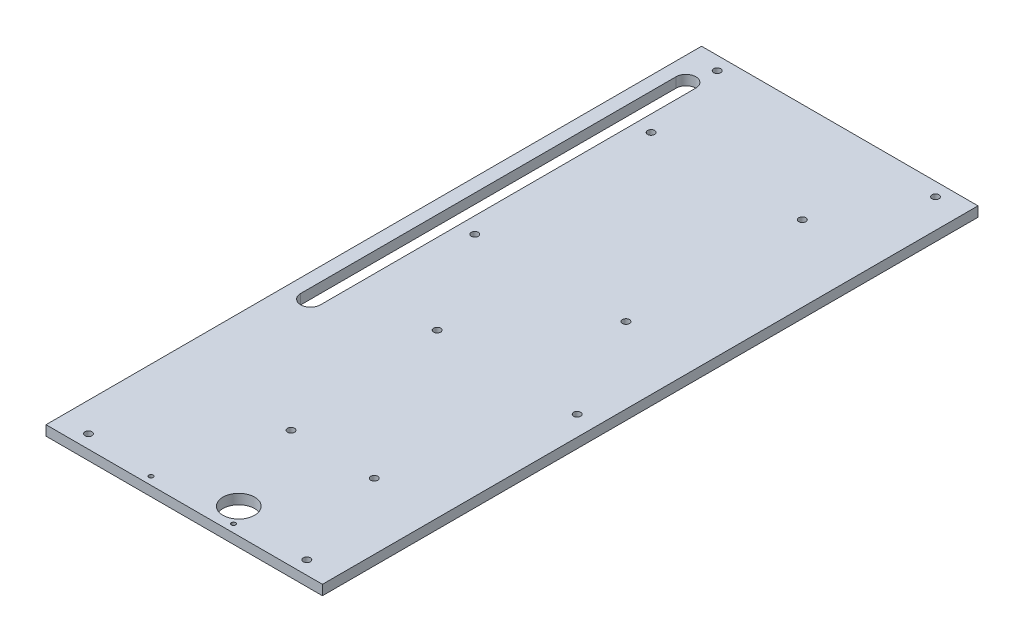
SolidWorks part; units mm, degrees
ref_plane "Front Plane" through (0, 0, 0) normal (0, 0, 1) x (1, 0, 0)
ref_plane "Top Plane" through (0, 0, 0) normal (0, 1, 0) x (1, 0, 0)
ref_plane "Right Plane" through (0, 0, 0) normal (1, 0, 0) x (0, 0, -1)
sketch "Sketch2" plane through (0, 0, 0) normal (0, 0, 1) x (1, 0, 0)
  line L0 (42.8242, -21.393) -> (42.8242, -24.5934)
  line L1 (0, -21.393) -> (0, -24.5934) construction
  line L2 (-46.0758, -24.5934) -> (42.8242, -24.5934)
  line L3 (-46.0758, -21.393) -> (-46.0758, -24.5934)
  line L4 (-46.0758, -21.393) -> (42.8242, -21.393)
  dimension "D1" = 88.9
  dimension "D2" = 3.2004
extrude "Boss-Extrude1" add sketch "Sketch2" along normal blind 210.82 contours L2 L0 L4 L3
sketch "Sketch3" plane through (0, -21.393, 0) normal (0, 1, 0) x (-1, 0, 0)
  line L0 (-42.8242, 208.28) -> (46.0758, 208.28) construction
  line L1 (38.5043, 9.421) -> (38.5043, 0) construction
  line L2 (46.0758, 0) -> (-42.8242, 0) construction
  line L3 (46.0758, 210.82) -> (-42.8242, 210.82) construction
  line L4 (36.73, 206.502) -> (46.0758, 206.502) construction
  line L5 (46.0758, 72.9493) -> (41.6793, 72.9493) construction
  line L6 (35.3293, 12.596) -> (41.6793, 12.596) construction
  line L7 (35.3293, 12.596) -> (35.3293, 133.3026)
  line L8 (35.3293, 133.3026) -> (41.6793, 133.3026) construction
  line L9 (41.6793, 12.596) -> (41.6793, 133.3026)
  line L10 (46.0758, 210.82) -> (-42.8242, 210.82) construction
  line L11 (-11.6838, 208.28) -> (-11.6838, 210.82) construction
  line L12 (-11.6838, 202.5188) -> (-11.6838, 208.28) construction
  line L13 (-7.6198, 202.5188) -> (-11.6838, 202.5188) construction
  line L14 (-42.8242, 210.82) -> (-42.8242, 0) construction
  line L15 (46.0758, 210.82) -> (46.0758, 0) construction
  line L16 (-33.4785, 206.502) -> (-33.4785, 210.82) construction
  line L17 (-33.4785, 206.502) -> (-42.8242, 206.502) construction
  line L18 (36.73, 206.502) -> (36.73, 210.82) construction
  line L19 (-33.4785, 4.318) -> (-42.8242, 4.318) construction
  line L20 (-33.4785, 4.318) -> (-33.4785, 0) construction
  line L21 (46.0758, 0) -> (-42.8242, 0) construction
  line L22 (36.73, 4.318) -> (36.73, 0) construction
  line L23 (36.73, 4.318) -> (46.0758, 4.318) construction
  line L24 (-18.451, 32.1211) -> (-18.451, 0) construction
  line L25 (-42.8242, 32.1211) -> (-18.451, 32.1211) construction
  line L26 (-18.451, 32.1211) -> (30.1646, 32.1211) construction
  line L27 (-18.451, 32.1211) -> (-18.451, 88.8393) construction
  line L28 (30.1646, 32.1211) -> (30.1646, 88.8393) construction
  line L29 (-18.451, 88.8393) -> (30.1646, 88.8393) construction
  line L30 (-42.8242, 122.5046) -> (-36.4214, 122.5046) construction
  line L31 (-36.4214, 122.5046) -> (-36.4214, 0) construction
  line L32 (5.127, 172.9556) -> (9.5159, 121.5883) construction
  line L33 (-21.6121, 172.9556) -> (5.127, 172.9556) construction
  line L34 (60.367, -163.7177) -> (66.7698, -163.7177) construction
  line L35 (66.7698, -163.7177) -> (96.7645, -163.7177) construction
  line L36 (-21.6121, 172.9556) -> (-36.4214, 122.5046) construction
  line L37 (81.5791, -113.2668) -> (108.3182, -113.2668) construction
  line L38 (81.5791, -113.2668) -> (66.7698, -163.7177) construction
  line L39 (76.3923, -158.9273) -> (82.7952, -158.9273) construction
  line L40 (82.7952, -158.9273) -> (112.7898, -158.9273) construction
  line L41 (97.6044, -108.4763) -> (124.3436, -108.4763) construction
  line L42 (97.6044, -108.4763) -> (82.7952, -158.9273) construction
  circle A0 centre (14.8338, 208.28) radius 0.6731
  arc A1 (35.3293, 133.3026) -> (41.6793, 133.3026) centre (38.5043, 133.3026) cw
  arc A2 (41.6793, 12.596) -> (35.3293, 12.596) centre (38.5043, 12.596) cw
  circle A3 centre (-11.6838, 208.28) radius 0.6731
  circle A4 centre (-7.6198, 202.5188) radius 5.08
  circle A5 centre (-33.4785, 206.502) radius 1.1303
  circle A6 centre (36.73, 206.502) radius 1.1303
  circle A7 centre (-33.4785, 4.318) radius 1.1303
  circle A8 centre (36.73, 4.318) radius 1.1303
  circle A9 centre (-18.451, 32.1211) radius 1.1303
  circle A10 centre (-18.451, 88.8393) radius 1.1303
  circle A11 centre (30.1646, 88.8393) radius 1.1303
  circle A12 centre (30.1646, 32.1211) radius 1.1303
  circle A13 centre (-21.6121, 172.9556) radius 1.1303
  circle A14 centre (-36.4214, 122.5046) radius 1.1303
  circle A15 centre (5.127, 172.9556) radius 1.1303
  circle A16 centre (9.5159, 121.5883) radius 1.1303
  circle A17 centre (81.5791, -113.2668) radius 1.1303
  circle A18 centre (66.7698, -163.7177) radius 1.1303
  circle A19 centre (108.3182, -113.2668) radius 1.1303
  circle A20 centre (97.6044, -108.4763) radius 1.1303
  circle A21 centre (82.7952, -158.9273) radius 1.1303
  circle A22 centre (124.3436, -108.4763) radius 1.1303
  circle A23 centre (112.7898, -158.9273) radius 1.1303
  point P12 (1.6258, 208.28)
  dimension "D5" = 1.3462
  dimension "D9" = 10.16
  dimension "D13" = 2.2606
  dimension "D15" = 9.3458
  dimension "D2" = 4.3965
  dimension "D3" = 120.7066
  dimension "D4" = 6.35
  dimension "D6" = 2.54
  dimension "D7" = 26.5176
  dimension "D8" = 13.208
  dimension "D10" = 5.7612
  dimension "D11" = 4.064
  dimension "D12" = 9.421
  dimension "D14" = 4.318
  dimension "D16" = 24.3732
  dimension "D17" = 32.1211
  dimension "D18" = 48.6156
  dimension "D19" = 56.7182
  dimension "D20" = 6.4028
  dimension "D21" = 122.5046
  dimension "D23" = 106.359
  dimension "D24" = 26.7391
  dimension "D25" = 52.5796
  dimension "D26" = 6.4028
  dimension "D27" = 29.9946
  dimension "D28" = 26.7391
  dimension "D29" = 73.641
  dimension "D30" = 52.5796
  dimension "D31" = 6.4028
  dimension "D32" = 29.9946
  dimension "D33" = 26.7391
  dimension "D34" = 73.641
  dimension "D35" = 52.5796
  dimension "D42" = 51.5544
  dimension "D43" = 94.884
extrude "Cut-Extrude1" cut sketch "Sketch3" against normal through all
sketch "Sketch4" plane through (0, 0, 0) normal (0, 0, -1) x (-1, 0, 0)
  line L0 (1.6258, -21.393) -> (1.6258, -24.5934) construction
  line L1 (46.0758, -21.393) -> (-42.8242, -21.393) construction
  line L2 (46.0758, -24.5934) -> (-42.8242, -24.5934) construction
sketch "Sketch5" plane through (42.8242, 0, 0) normal (1, 0, 0) x (0, 0, -1)
  line L0 (-105.41, -21.393) -> (-105.41, -24.5934) construction
  line L1 (-210.82, -21.393) -> (0, -21.393) construction
  line L2 (-210.82, -24.5934) -> (0, -24.5934) construction
